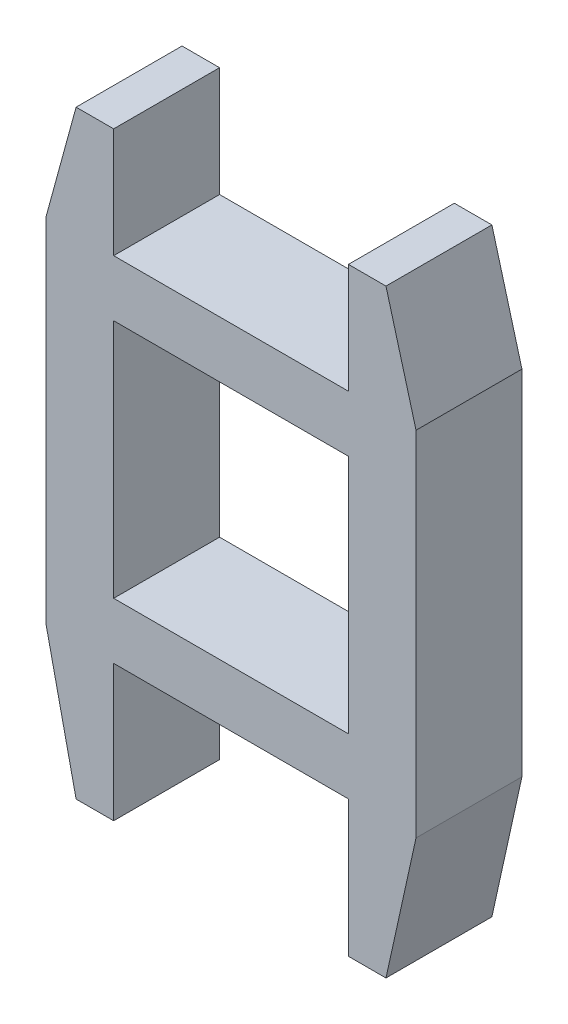
SolidWorks part; units mm, degrees
material "Acrylic (Medium-high impact)"
ref_plane "Front Plane" through (0, 0, 0) normal (0, 0, 1) x (1, 0, 0)
ref_plane "Top Plane" through (0, 0, 0) normal (0, 1, 0) x (1, 0, 0)
ref_plane "Right Plane" through (0, 0, 0) normal (1, 0, 0) x (0, 0, -1)
sketch "Sketch1" plane through (0, 0, 0) normal (0, 0, 1) x (1, 0, 0)
  line L0 (1247.1596, 962.2772) -> (1247.1596, 949.4772)
  line L1 (1263.2596, 947.9772) -> (1243.5596, 947.9772) construction
  line L2 (1247.1596, 946.4772) -> (1243.5596, 946.4772) construction
  line L3 (1247.1596, 962.2772) -> (1259.6596, 962.2772)
  line L4 (1245.1596, 971.1264) -> (1247.1596, 971.1264)
  line L5 (1247.1596, 971.1264) -> (1247.1596, 965.2772)
  line L6 (1247.1596, 955.8772) -> (1259.6596, 955.8772) construction
  line L7 (1259.6596, 965.2772) -> (1247.1596, 965.2772)
  line L8 (1243.5596, 965.2772) -> (1243.5596, 946.4772)
  line L9 (1243.5596, 946.4772) -> (1245.1596, 939.218)
  line L10 (1247.1596, 965.2772) -> (1243.5596, 965.2772) construction
  line L11 (1259.6596, 946.4772) -> (1247.1596, 946.4772)
  line L12 (1243.5596, 965.2772) -> (1245.1596, 971.1264)
  line L13 (1247.1596, 939.218) -> (1247.1596, 946.4772)
  line L14 (1245.1596, 939.218) -> (1247.1596, 939.218)
  line L15 (1247.1596, 949.4772) -> (1259.6596, 949.4772)
  line L16 (1259.6596, 965.2772) -> (1263.2596, 965.2772) construction
  line L17 (1259.6596, 946.4772) -> (1263.2596, 946.4772) construction
  line L18 (1261.6596, 939.218) -> (1259.6596, 939.218)
  line L19 (1253.4096, -39.6851) -> (1253.4096, 49960.3149) construction
  line L20 (1259.6596, 939.218) -> (1259.6596, 946.4772)
  line L21 (1263.2596, 965.2772) -> (1261.6596, 971.1264)
  line L22 (1263.2596, 946.4772) -> (1261.6596, 939.218)
  line L23 (1263.2596, 965.2772) -> (1263.2596, 946.4772)
  line L24 (1259.6596, 971.1264) -> (1259.6596, 965.2772)
  line L25 (1261.6596, 971.1264) -> (1259.6596, 971.1264)
  line L26 (1263.2596, 963.7772) -> (1243.5596, 963.7772) construction
  line L27 (1259.6596, 962.2772) -> (1259.6596, 949.4772)
  point P2 (1263.2596, 955.8772)
  point P14 (1243.5596, 955.8772)
  point P15 (1253.4096, 965.2772)
  point P20 (1253.4096, 963.7772)
  point P26 (1253.4096, 955.8772)
  point P28 (1253.4096, 965.2772)
  point P30 (1253.4096, 962.2772)
  point P31 (1253.4096, 947.9772)
  point P33 (1253.4096, 949.4772)
  point P36 (1253.4096, 946.4772)
  point P38 (1253.4096, 962.2772)
  dimension "D1" = 6.25
  dimension "D2" = 5.8492
  dimension "D3" = 2
  dimension "D4" = 3
  dimension "D5" = 9.4
  dimension "D6" = 7.2592
  dimension "D7" = 192.43
  dimension "D8" = 3.6
extrude "Boss-Extrude1" add sketch "Sketch1" along normal blind 5.64
